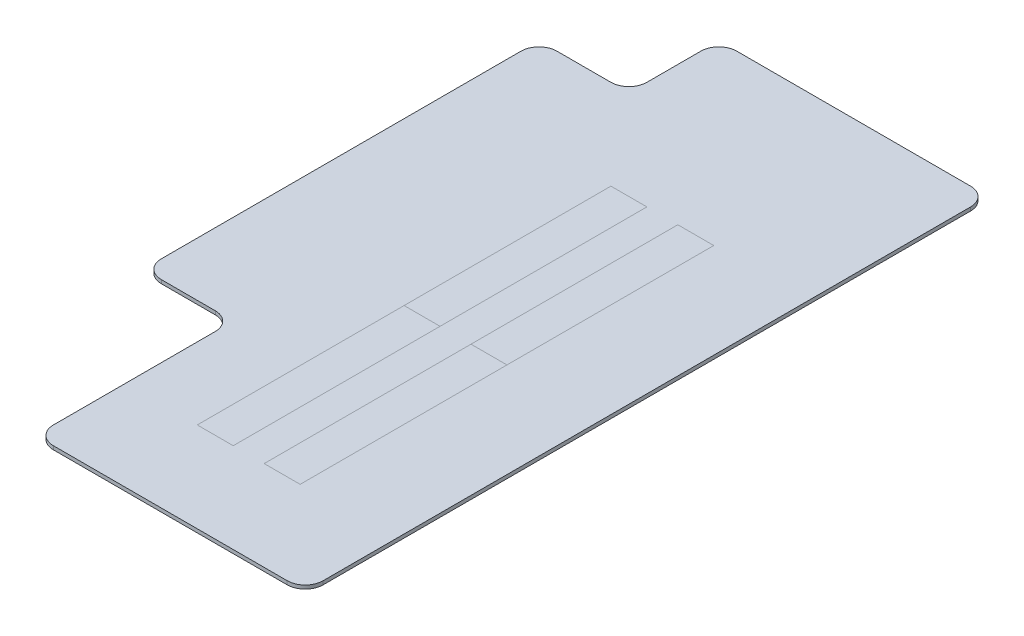
SolidWorks part; units mm, degrees
material "1.0116 (S235J2G3)"
ref_plane "Front Plane" through (0, 0, 0) normal (0, 0, 1) x (1, 0, 0)
ref_plane "Top Plane" through (0, 0, 0) normal (0, 1, 0) x (1, 0, 0)
ref_plane "Right Plane" through (0, 0, 0) normal (1, 0, 0) x (0, 0, -1)
sketch "Sketch2" plane through (0, 0, 0) normal (0, 1, 0) x (1, 0, 0)
  line L0 (-1000, 1600) -> (-1000, 600)
  line L1 (-950, 550) -> (-800, 550)
  line L2 (-750, 500) -> (-750, 50)
  line L3 (-700, 0) -> (-50, 0)
  line L4 (0, 50) -> (0, 1850)
  line L5 (-50, 1900) -> (-700, 1900)
  line L6 (-750, 1850) -> (-750, 1700)
  line L7 (-800, 1650) -> (-950, 1650)
  arc A0 (-50, 0) -> (0, 50) centre (-50, 50) ccw
  arc A1 (-750, 50) -> (-700, 0) centre (-700, 50) ccw
  arc A2 (-800, 550) -> (-750, 500) centre (-800, 500) cw
  arc A3 (-1000, 600) -> (-950, 550) centre (-950, 600) ccw
  arc A4 (-750, 1700) -> (-800, 1650) centre (-800, 1700) cw
  arc A5 (-1000, 1600) -> (-950, 1650) centre (-950, 1600) cw
  arc A6 (-700, 1900) -> (-750, 1850) centre (-700, 1850) ccw
  arc A7 (0, 1850) -> (-50, 1900) centre (-50, 1850) ccw
  point P11 (0, 0)
  point P16 (-750, 550)
  point P19 (-1000, 550)
  point P22 (-750, 1650)
  point P25 (-1000, 1650)
  point P28 (-750, 1900)
  dimension "D9" = 50
  dimension "D1" = 1000
  dimension "D2" = 1100
  dimension "D3" = 250
  dimension "D4" = 250
  dimension "D5" = 550
  dimension "D6" = 250
  dimension "D7" = 0
  dimension "D8" = 0
extrude "Boss-Extrude1" add sketch "Sketch2" along normal blind 10
sketch "Sketch3" plane through (0, 10, 0) normal (0, 1, 0) x (1, 0, 0)
  line L0 (-450, 1400) -> (-450, 250)
  line L1 (-450, 250) -> (-550, 250)
  line L2 (-550, 250) -> (-550, 1400)
  line L3 (-550, 1400) -> (-450, 1400)
  line L4 (-364, 250) -> (-364, 1400)
  line L5 (-364, 1400) -> (-264, 1400)
  line L6 (-264, 1400) -> (-264, 250)
  line L7 (-264, 250) -> (-364, 250)
  line L8 (-700, 0) -> (-50, 0) construction
  line L9 (-750, 500) -> (-750, 50) construction
  line L10 (-550, 825) -> (-450, 825)
  line L11 (-364, 825) -> (-264, 825)
  point P10 (-314, 250)
  dimension "D1" = 1150
  dimension "D2" = 1150
  dimension "D3" = 100
  dimension "D4" = 86
  dimension "D5" = 100
  dimension "D6" = 250
  dimension "D7" = 200
  dimension "D8" = 250
split line "Split Line1"
sketch "Sketch5" plane through (0, 0, 0) normal (0, -1, 0) x (1, 0, 0)
  line L0 (-930, -550) -> (-930, -1650)
  line L1 (-950, -550) -> (-800, -550) construction
  line L2 (-800, -1650) -> (-950, -1650) construction
  line L3 (-930, -1650) -> (-880, -1650)
  line L4 (-880, -1650) -> (-880, -550)
  line L5 (-1000, -1600) -> (-1000, -600) construction
  line L6 (-750, -434.7223) -> (-750, -376.9873)
  line L7 (-750, -500) -> (-750, -50) construction
  line L8 (-750, -376.9873) -> (0, -810)
  line L9 (0, -50) -> (0, -1850) construction
  line L10 (0, -810) -> (0, -867.735)
  line L11 (0, -867.735) -> (-750, -434.7223)
  line L17 (-700, 0) -> (-50, 0) construction
  line L24 (-750, -1775.2777) -> (0, -1342.265)
  line L25 (-750, -1850) -> (-750, -1700) construction
  line L26 (0, -1342.265) -> (0, -1400)
  line L27 (0, -1400) -> (-750, -1833.0127)
  line L28 (-750, -1833.0127) -> (-750, -1775.2777)
  line L29 (-50, -1900) -> (-700, -1900) construction
  dimension "D1" = 70
  dimension "D2" = 50
  dimension "D3" = 50
  dimension "D4" = 30
  dimension "D5" = 120
  dimension "D6" = 500
  dimension "D7" = 50
  dimension "D8" = 810
split line "Split Line2"
